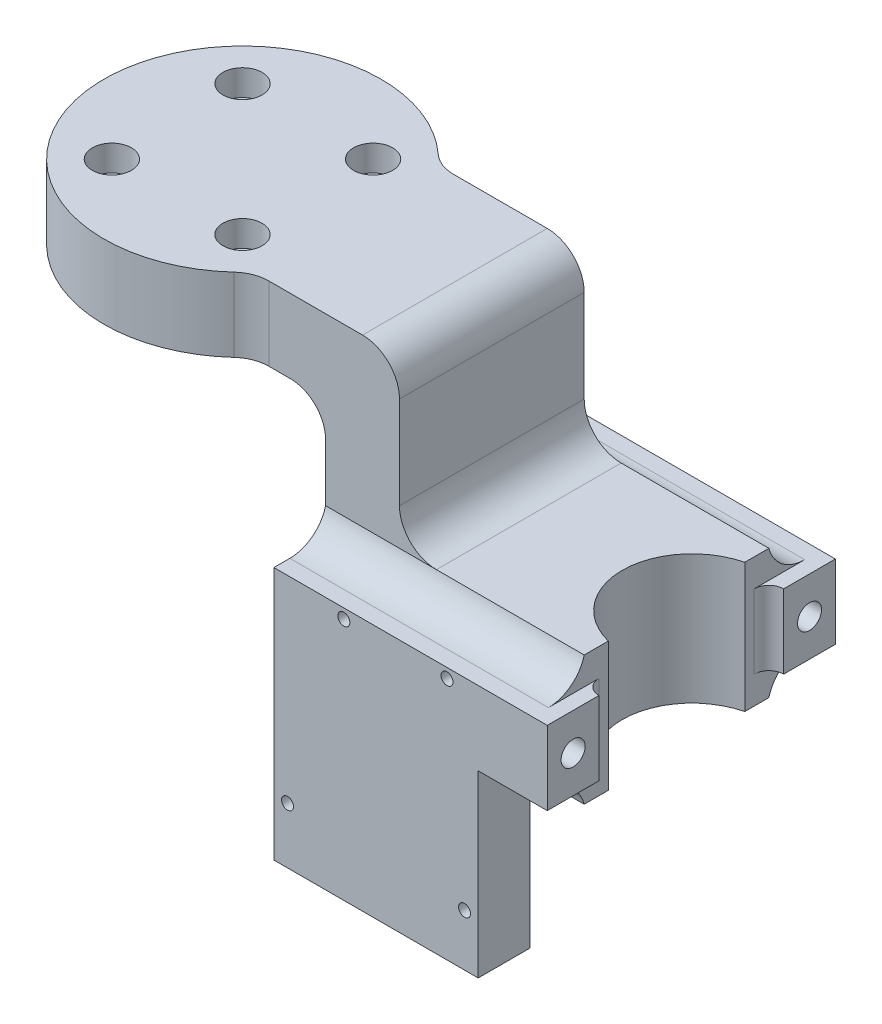
SolidWorks part; units mm, degrees
note: The reader was unsure of these and kept them because the rebuilt part matched: shared geometry of "Sketch13<3>", "Sketch16<3>".
material "PLA (weight) "
ref_plane "Front Plane" through (0, 0, 0) normal (0, 0, 1) x (1, 0, 0)
ref_plane "Top Plane" through (0, 0, 0) normal (0, 1, 0) x (1, 0, 0)
ref_plane "Right Plane" through (0, 0, 0) normal (1, 0, 0) x (0, 0, -1)
sketch "Sketch1" plane through (0, 0, 0) normal (0, 1, 0) x (1, 0, 0)
  line L1 (-25, 25) -> (25, 25)
  line L2 (-25, 25) -> (-25, -25)
  line L3 (-25, -25) -> (25, -25)
  line L4 (25, 25) -> (25, -25)
  line L5 (-25, 25) -> (25, -25) construction
  line L6 (-25, -25) -> (25, 25) construction
  ellipse E0 centre (0, 0) end of major axis (19.7, 0) minor radius 19.1
  dimension "D1" = 39.4
  dimension "D2" = 38.2
  dimension "D3" = 50
  dimension "D4" = 50
extrude "Boss-Extrude1" add sketch "Sketch1" along normal blind 35
sketch "Sketch2" plane through (0, 35, 0) normal (0, 1, 0) x (1, 0, 0)
  line L0 (25, 25) -> (-25, 25) construction
  line L1 (-5, 25) -> (25, 25)
  line L2 (-5, 25) -> (-5, -25)
  line L3 (-5, -25) -> (25, -25)
  line L4 (25, 25) -> (25, -25)
  dimension "D1" = 30
extrude "Cut-Extrude1" cut sketch "Sketch2" against normal blind 35
sketch "Sketch3" plane through (0, 35, 0) normal (0, 1, 0) x (1, 0, 0)
  line L0 (-25, -25) -> (-5, -25) construction
  line L1 (-25, 25) -> (-12, 25)
  line L2 (-25, 25) -> (-25, -25)
  line L3 (-25, -25) -> (-12, -25)
  line L4 (-12, 25) -> (-12, -25)
  dimension "D1" = 13
extrude "Boss-Extrude2" add sketch "Sketch3" along normal blind 20
sketch "Sketch4" plane through (-25, 0, 0) normal (-1, 0, 0) x (0, 0, 1)
  line L4 (18.4746, 0) -> (18.4746, 35)
  line L5 (-18.4746, 0) -> (18.4746, 0)
  line L6 (-18.4746, 35) -> (-18.4746, 0)
  line L7 (-15.1475, 35) -> (-18.4746, 35)
  line L8 (18.4746, 0) -> (18.4746, 35)
  line L9 (-18.4746, 0) -> (18.4746, 0)
  line L10 (-18.4746, 35) -> (-18.4746, 0)
  line L11 (-15.1475, 35) -> (-18.4746, 35)
  line L14 (15.1475, 35) -> (-15.1475, 35)
  line L16 (15.1475, 35) -> (-15.1475, 35)
  line L18 (18.4746, 35) -> (15.1475, 35)
  line L20 (18.4746, 35) -> (15.1475, 35)
  circle A0 centre (18.4746, 50) radius 1.5
  dimension "D3" = 3
  dimension "D1" = 0
extrude "Cut-Extrude2" cut sketch "Sketch4" against normal through all contours A0
ref_plane "Plane1" through (-12, 55, -25) normal (-1, 0, 0) x (0, 0, 1)
sketch "Sketch5" plane through (-12, 55, -25) normal (-1, 0, 0) x (0, 0, 1)
  line L1 (0, 0) -> (36.9746, 0)
  line L2 (0, 0) -> (0, -20)
  line L3 (0, -20) -> (36.9746, -20)
  line L4 (0, -55) -> (50, -55)
  line L5 (50, -55) -> (50, 0)
  line L6 (50, 0) -> (0, 0)
  line L7 (0, 0) -> (0, -55)
  line L8 (0, -55) -> (50, -55)
  line L9 (50, -55) -> (50, 0)
  line L11 (0, 0) -> (0, -55) construction
  line L12 (43.4746, -55) -> (43.4746, -20)
  line L13 (6.5254, -55) -> (43.4746, -55)
  line L14 (6.5254, -20) -> (6.5254, -55)
  line L15 (9.8525, -20) -> (6.5254, -20)
  line L16 (43.4746, -55) -> (43.4746, -20) construction
  line L17 (6.5254, -55) -> (43.4746, -55)
  line L18 (6.5254, -20) -> (6.5254, -55) construction
  line L19 (9.8525, -20) -> (6.5254, -20) construction
  line L20 (36.9746, 0) -> (36.9746, -20)
  line L24 (50, 0) -> (0, 0)
  line L27 (40.1475, -20) -> (9.8525, -20)
  line L28 (40.1475, -20) -> (9.8525, -20)
  line L29 (43.4746, -20) -> (40.1475, -20)
  line L30 (43.4746, -20) -> (40.1475, -20)
  circle A0 centre (43.4746, -5) radius 1.5 construction
  dimension "D3" = 6.5
  dimension "D1" = 0
  dimension "D2" = 0
extrude "Cut-Extrude3" cut sketch "Sketch5" along normal blind 20 contours L20 L1 L2 L3
sketch "Sketch6" plane through (-5, 0, 0) normal (1, 0, 0) x (0, 0, -1)
  line L0 (-25, 35) -> (-25, 0) construction
  line L1 (25, 0) -> (25, 35) construction
  line L2 (-39, 27.5) -> (-25, 27.5)
  line L3 (-39, 27.5) -> (-39, 7.5)
  line L4 (-39, 7.5) -> (-25, 7.5)
  line L5 (-25, 27.5) -> (-25, 7.5)
  line L6 (-39, 27.5) -> (-25, 7.5) construction
  line L7 (-39, 7.5) -> (-25, 27.5) construction
  line L8 (39, 7.5) -> (25, 7.5)
  line L9 (39, 7.5) -> (39, 27.5)
  line L10 (39, 27.5) -> (25, 27.5)
  line L11 (25, 7.5) -> (25, 27.5)
  line L12 (39, 7.5) -> (25, 27.5) construction
  line L13 (39, 27.5) -> (25, 7.5) construction
  line L14 (32, 17.5) -> (-26.1195, 17.5) construction
  circle A0 centre (32, 17.5) radius 3.25
  circle A1 centre (-32, 17.5) radius 3.25
  point P4 (-32, 17.5)
  point P9 (32, 17.5)
  point P17 (-25, 17.5)
  point P18 (-25, 17.5)
  point P19 (25, 17.5)
  point P20 (25, 17.5)
  dimension "D4" = 6.5
  dimension "D5" = 6.5
  dimension "D2" = 20
  dimension "D1" = 14
  dimension "D3" = 14
extrude "Boss-Extrude3" add sketch "Sketch6" along normal blind 4 and the other way blind 20
sketch "Sketch7" plane through (-25, 0, 0) normal (-1, 0, 0) x (0, 0, 1)
  circle A0 centre (-32, 17.5) radius 5.3
  circle A1 centre (32, 17.5) radius 5.3
  circle A2 centre (18.4746, 50) radius 3
  dimension "D1" = 10.6
  dimension "D2" = 10.6
  dimension "D3" = 6
extrude "Cut-Extrude4" cut sketch "Sketch7" against normal blind 6
sketch "Sketch8" plane through (0, 35, 0) normal (0, 1, 0) x (1, 0, 0)
  line L4 (-12, -11.9746) -> (-25, -11.9746)
  line L5 (-25, -11.9746) -> (-25, -25)
  line L6 (-25, -25) -> (-12, -25)
  line L7 (-12, -25) -> (-12, -11.9746)
  line L8 (-12, -11.9746) -> (-25, -11.9746)
  line L9 (-25, -11.9746) -> (-25, -25)
  line L10 (-25, -25) -> (-12, -25)
  line L11 (-12, -25) -> (-12, -11.9746)
  dimension "D1" = 0
extrude "Cut-Extrude5" cut sketch "Sketch8" along normal blind 30
fillet "Fillet6" radius 4 2 edges at (-5, 17.5, 25) (-5, 17.5, -25)
fillet "Fillet5" radius 10 4 edges at (-15, 7.5, 25) (-15, 27.5, 25) (-15, 27.5, -25) (-15, 7.5, -25)
sketch "Sketch9" plane through (-25, 0, 0) normal (-1, 0, 0) x (0, 0, 1)
  line L4 (39, 27.5) -> (34.6825, 27.5)
  line L6 (39, 27.5) -> (34.6825, 27.5)
  line L9 (25, 35) -> (-25, 35)
  line L13 (-25, 0) -> (25, 0)
  line L14 (-34.6825, 27.5) -> (-39, 27.5)
  line L15 (-34.6825, 27.5) -> (-39, 27.5)
  line L17 (25, 35) -> (-25, 35)
  line L21 (-25, 0) -> (25, 0)
  line L24 (-39, 27.5) -> (-39, 7.5)
  line L25 (-39, 27.5) -> (-39, 7.5)
  line L26 (-39, 7.5) -> (-34.6825, 7.5)
  line L27 (-39, 7.5) -> (-34.6825, 7.5)
  line L28 (34.6825, 7.5) -> (39, 7.5)
  line L29 (34.6825, 7.5) -> (39, 7.5)
  line L30 (39, 7.5) -> (39, 27.5)
  line L31 (39, 7.5) -> (39, 27.5)
  circle A0 centre (32, 17.5) radius 5.3 construction
  circle A1 centre (-32, 17.5) radius 5.3 construction
  circle A2 centre (32, 17.5) radius 5.3
  circle A3 centre (-32, 17.5) radius 5.3
  arc A12 (25, 35) -> (34.6825, 27.5) centre (34.6825, 37.5) ccw
  arc A13 (25, 35) -> (34.6825, 27.5) centre (34.6825, 37.5) ccw
  arc A14 (-34.6825, 27.5) -> (-25, 35) centre (-34.6825, 37.5) ccw
  arc A15 (-34.6825, 27.5) -> (-25, 35) centre (-34.6825, 37.5) ccw
  arc A16 (-25, 0) -> (-34.6825, 7.5) centre (-34.6825, -2.5) ccw
  arc A17 (-25, 0) -> (-34.6825, 7.5) centre (-34.6825, -2.5) ccw
  arc A18 (34.6825, 7.5) -> (25, 0) centre (34.6825, -2.5) ccw
  arc A19 (34.6825, 7.5) -> (25, 0) centre (34.6825, -2.5) ccw
  dimension "D1" = 0
extrude "Boss-Extrude4" add sketch "Sketch9" along normal blind 50
sketch "Sketch10" plane through (0, 35, 0) normal (0, 1, 0) x (1, 0, 0)
  line L5 (-75, -25) -> (-5, -25) construction
  line L6 (-75, 25) -> (-55, 25)
  line L7 (-75, 25) -> (-75, -25)
  line L8 (-75, -25) -> (-55, -25)
  line L9 (-55, 25) -> (-55, -25)
  dimension "D1" = 20
extrude "Boss-Extrude5" add sketch "Sketch10" along normal blind 45
fillet "Fillet7" radius 10 1 edges at (-55, 35, 0)
sketch "Sketch11" plane through (-75, 0, 0) normal (-1, 0, 0) x (0, 0, 1)
  line L5 (25, 80) -> (25, 35) construction
  line L6 (-25, 80) -> (25, 80)
  line L7 (-25, 80) -> (-25, 60)
  line L8 (-25, 60) -> (25, 60)
  line L9 (25, 80) -> (25, 60)
  dimension "D1" = 20
extrude "Boss-Extrude6" add sketch "Sketch11" along normal blind 85
sketch "Sketch13" plane through (0, 80, 0) normal (0, 1, 0) x (1, 0, 0)
  line L0 (-85, 25) -> (-85, -25) construction
  line L1 (-55, 25) -> (-160, 25) construction
  line L2 (-55, 25) -> (-160, 25) construction
  line L3 (-160, -25) -> (-55, -25) construction
  line L4 (-85, 0) -> (-160, 0) construction
  line L5 (-160, 25) -> (-150.4508, 25)
  line L6 (-160, 25) -> (-160, -25)
  line L7 (-160, -25) -> (-150.4508, -25)
  line L8 (-160, -25) -> (-160, 25) construction
  circle A0 centre (-122.5, 0) radius 37.5
  point P19 (-160, 0)
  dimension "D2" = 75
  dimension "D1" = 75
extrude "Boss-Extrude7" add sketch "Sketch13" against normal up to surface (20 mm away) up to face at (-117.5, 60, 0)
fillet "Fillet8" radius 9.5 1 edges at (-75, 60, 0)
extrude "Cut-Extrude6" cut sketch "Sketch13<3>" against normal blind 85
sketch "Sketch13<3>" plane through (0, 80, 0) normal (0, 1, 0) x (1, 0, 0) same geometry as "Sketch13"
fillet "Fillet9" radius 10 2 edges at (-94.5492, 70, -25) (-94.5492, 70, 25)
fillet "Fillet10" radius 10 1 edges at (-55, 80, 0)
sketch "Sketch14" plane through (0, 80, 0) normal (0, 1, 0) x (1, 0, 0)
  line L0 (-122.5, 25) -> (-122.5, -25) construction
  line L1 (-122.5, -25) -> (-97.5, 0) construction
  line L2 (-97.5, 0) -> (-122.5, 25) construction
  line L3 (-122.5, 25) -> (-147.5, 0) construction
  line L4 (-147.5, 0) -> (-97.5, 0) construction
  line L5 (-147.5, 0) -> (-122.5, -25) construction
  line L6 (-140.1777, -17.6777) -> (-104.8223, 17.6777) construction
  line L7 (-140.1777, 17.6777) -> (-104.8223, -17.6777) construction
  circle A0 centre (-122.5, 0) radius 25 construction
  circle A1 centre (-140.1777, 17.6777) radius 3.25
  circle A2 centre (-140.1777, -17.6777) radius 3.25
  circle A3 centre (-104.8223, -17.6777) radius 3.25
  circle A4 centre (-104.8223, 17.6777) radius 3.25
  point P10 (-122.5, 0)
  point P13 (-122.5, 0)
  dimension "D4" = 6.5
  dimension "D5" = 6.5
  dimension "D1" = 50
  dimension "D2" = 6.5
  dimension "D3" = 6.5
extrude "Cut-Extrude7" cut sketch "Sketch14" against normal blind 85
sketch "Sketch15" plane through (0, 80, 0) normal (0, 1, 0) x (1, 0, 0)
  circle A0 centre (-140.1777, 17.6777) radius 5.3
  circle A1 centre (-140.1777, -17.6777) radius 5.3
  circle A2 centre (-104.8223, -17.6777) radius 5.3
  circle A3 centre (-104.8223, 17.6777) radius 5.3
  dimension "D1" = 10.6
  dimension "D2" = 10.6
  dimension "D3" = 10.6
  dimension "D4" = 10.6
extrude "Cut-Extrude8" cut sketch "Sketch15" against normal blind 7
sketch "Sketch16" plane through (-75, 0, 0) normal (-1, 0, 0) x (0, 0, 1)
  line L1 (-25.9378, 17.5) -> (-28.9689, 22.75)
  line L2 (-28.9689, 22.75) -> (-35.0311, 22.75)
  line L3 (-35.0311, 22.75) -> (-38.0622, 17.5)
  line L4 (-38.0622, 17.5) -> (-35.0311, 12.25)
  line L5 (-35.0311, 12.25) -> (-28.9689, 12.25)
  line L6 (-28.9689, 12.25) -> (-25.9378, 17.5)
  line L7 (25.9378, 17.5) -> (28.9689, 12.25)
  line L8 (28.9689, 12.25) -> (35.0311, 12.25)
  line L9 (35.0311, 12.25) -> (38.0622, 17.5)
  line L10 (38.0622, 17.5) -> (35.0311, 22.75)
  line L11 (35.0311, 22.75) -> (28.9689, 22.75)
  line L12 (28.9689, 22.75) -> (25.9378, 17.5)
  circle A0 centre (-32, 17.5) radius 5.25 construction
  circle A1 centre (32, 17.5) radius 5.25 construction
  circle A2 centre (32, 17.5) radius 3.25 construction
  circle A3 centre (-32, 17.5) radius 3.25 construction
  circle A4 centre (32, 17.5) radius 3.25
  circle A5 centre (-32, 17.5) radius 3.25
  dimension "D1" = 10.5
  dimension "D2" = 10.5
extrude "Boss-Extrude9" add sketch "Sketch16" against normal up to surface (56 mm away) up to face at (-19, 17.5, -26.7)
extrude "Cut-Extrude11" cut sketch "Sketch16<3>" against normal blind 10
sketch "Sketch16<3>" plane through (-75, 0, 0) normal (-1, 0, 0) x (0, 0, 1) same geometry as "Sketch16"
sketch "Sketch17" plane through (0, 0, 0) normal (0, -1, 0) x (1, 0, 0)
  line L5 (-75, 39) -> (-1, 39) construction
  line L6 (-75, 25) -> (-60, 25)
  line L7 (-75, 25) -> (-75, 39)
  line L8 (-75, 39) -> (-60, 39)
  line L9 (-60, 25) -> (-60, 39)
  dimension "D1" = 15
extrude "Boss-Extrude10" add sketch "Sketch17" against normal up to surface (7.5 mm away) up to face at (-27.1381, 7.5, 32.3656)
sketch "Sketch18" plane through (0, 0, 0) normal (0, -1, 0) x (1, 0, 0)
  line L5 (-75, 39) -> (-60, 39)
  line L6 (-75, 39) -> (-75, 25)
  line L7 (-75, 25) -> (-60, 25)
  line L8 (-60, 39) -> (-60, 25)
extrude "Boss-Extrude11" add sketch "Sketch18" along normal blind 41.08
sketch "Sketch20" plane through (0, 7.5, 0) normal (0, -1, 0) x (1, 0, 0)
  line L1 (-60, 39) -> (-19.7, 39)
  line L2 (-60, 39) -> (-60, 25)
  line L4 (-19.7, 39) -> (-19.7, 25)
  line L5 (-60, 39) -> (-1, 39) construction
  line L6 (-60, 25) -> (-19.7, 25)
  ellipse E0 centre (0, 0) end of major axis (19.7, 0) minor radius 19.1 (-5, 18.4746) -> (-5, -18.4746) ccw construction
extrude "Boss-Extrude12" add sketch "Sketch20" along normal up to surface (48.58 mm away) up to face at (-67.5, -41.08, 32)
sketch "Sketch21" plane through (0, 0, 39) normal (0, 0, 1) x (1, 0, 0)
  line L0 (-75, -41.08) -> (-75, 27.5) construction
  line L1 (-75, 27.5) -> (-1, 27.5) construction
  circle A0 centre (-56.0686, 24.8647) radius 1.6193
  circle A1 centre (-28.1413, 24.8647) radius 1.6193
  circle A2 centre (-71.3086, -25.9226) radius 1.6193
  circle A3 centre (-23.3915, -27.0656) radius 1.6193
  dimension "D1" = 3.2385
  dimension "D2" = 27.9273
  dimension "D3" = 50.7873
  dimension "D4" = 2.6353
  dimension "D5" = 15.24
  dimension "D6" = 3.6914
  dimension "D7" = 51.9303
  dimension "D8" = 4.7498
extrude "Cut-Extrude13" cut sketch "Sketch21" against normal blind 7
equation "\"D3@Sketch6\"=\"D1@Sketch6\""
equation "\"D5@Sketch6\"=\"D4@Sketch6\""
equation "\"D2@Sketch7\"=\"D1@Sketch7\""
equation "\"D3@Sketch14\"=\"D2@Sketch14\""
equation "\"D4@Sketch14\"=\"D2@Sketch14\""
equation "\"D5@Sketch14\"=\"D2@Sketch14\""
equation "\"D3@Sketch15\"=\"D1@Sketch15\""
equation "\"D4@Sketch15\"=\"D1@Sketch15\""
equation "\"D2@Sketch15\"=\"D1@Sketch15\""
equation "\"D2@Sketch16\"=\"D1@Sketch16\""
